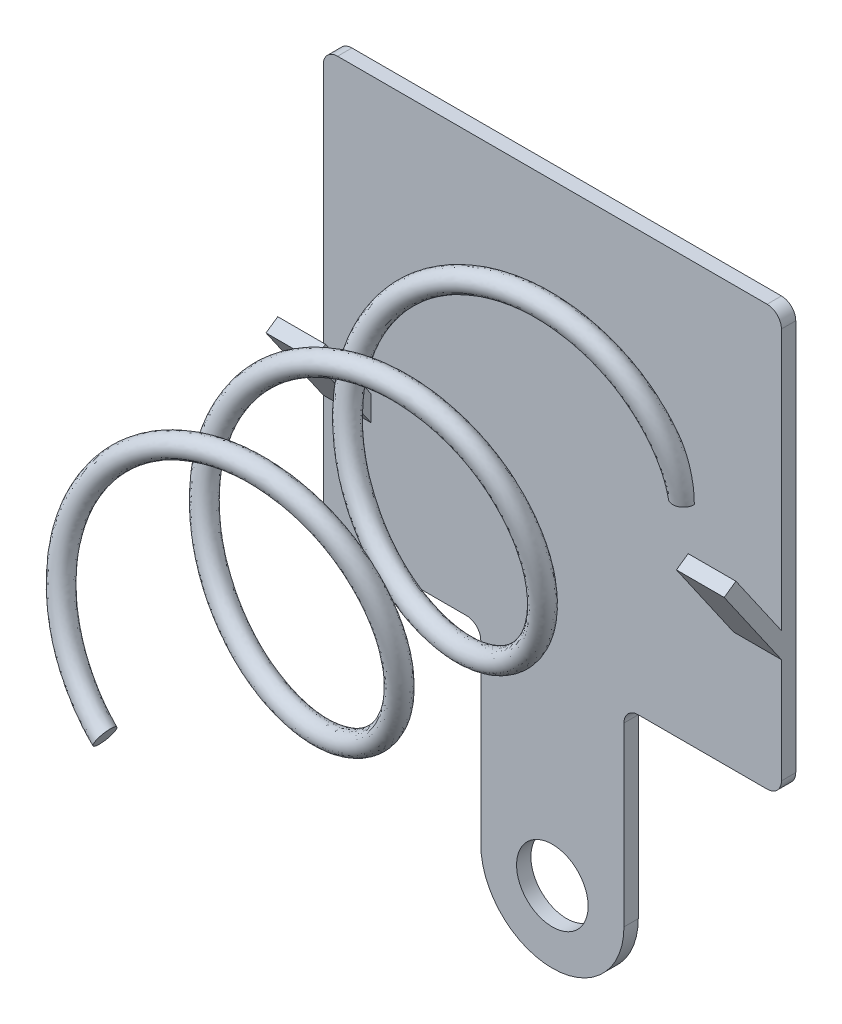
SolidWorks part; units mm, degrees
ref_plane "Front Plane" through (0, 0, 0) normal (0, 0, 1) x (1, 0, 0)
ref_plane "Top Plane" through (0, 0, 0) normal (0, 1, 0) x (1, 0, 0)
ref_plane "Right Plane" through (0, 0, 0) normal (1, 0, 0) x (0, 0, -1)
sketch "Sketch1" plane through (0, 0, 0) normal (0, 0, 1) x (1, 0, 0)
  line L0 (0, 0) -> (0, 4.4) construction
  line L1 (-4.8, 4.4) -> (4.8, 4.4)
  line L2 (4.8, 4.4) -> (4.8, -4.4)
  line L3 (4.8, -4.4) -> (1.5, -4.4)
  line L4 (1.5, -4.4) -> (1.5, -8.4)
  line L5 (0, 0) -> (0, -8.4) construction
  line L6 (-1.5, -4.4) -> (-1.5, -8.4)
  line L7 (-4.8, -4.4) -> (-1.5, -4.4)
  line L8 (-4.8, 4.4) -> (-4.8, -4.4)
  line L9 (-2.6852, -9.9) -> (3.5735, -9.9) construction
  line L10 (0, 0) -> (4.8, 0) construction
  arc A0 (1.5, -8.4) -> (-1.5, -8.4) centre (0, -8.4) cw
  circle A1 centre (0, -8.4) radius 0.75
  dimension "D5" = 1.5
  dimension "D1" = 9.6
  dimension "D2" = 8.8
  dimension "D3" = 14.3
  dimension "D4" = 3
extrude "Boss-Extrude1" add sketch "Sketch1" along normal blind 0.3
fillet "Fillet1" radius 0.3 6 edges at (-1.5, -4.4, 0.15) (1.5, -4.4, 0.15) (4.8, -4.4, 0.15) (-4.8, -4.4, 0.15) (-4.8, 4.4, 0.15) (4.8, 4.4, 0.15)
sketch "Sketch2" plane through (4.8, 0, 0) normal (1, 0, 0) x (0, 0, -1)
  line L0 (-0.3, -1.9) -> (-1.5, -0.1711)
  line L1 (-0.3, -4.1) -> (-0.3, 4.1) construction
  line L2 (-1.5, -0.1711) -> (-1.2535, 0)
  line L3 (-1.2535, 0) -> (-0.3, -1.3739)
  line L4 (-0.3, -1.3739) -> (-0.3, -1.9)
  line L5 (-0.3, 4.4) -> (0, 4.4) construction
  line L6 (0, -4.1) -> (0, 4.1) construction
  line L7 (0, -4.4) -> (-0.3, -4.4) construction
  dimension "D1" = 0.3
  dimension "D2" = 6.3
  dimension "D3" = 1.5
  dimension "D4" = 4.4
extrude "Boss-Extrude2" add sketch "Sketch2" against normal blind 1
mirror "Mirror1" about plane through (0, 0, 0) normal (1, 0, 0) of "Boss-Extrude2"
sketch "Sketch3" plane through (0, 0, 0.3) normal (0, 0, 1) x (1, 0, 0)
  circle A0 centre (0, 0) radius 2.75
  dimension "D1" = 5.5
curve "Helix/Spiral1" pitch 3 height 8 radius 2.75 centre (0, 0, 0.3) axis (0, 0, 1) start towards (1, 0, 0)
sketch "Sketch4" plane through (0, 0, 0) normal (0, 1, 0) x (1, 0, 0)
  line L0 (4.5, -0.3) -> (-4.5, -0.3) construction
  circle A0 centre (2.75, -0.3) radius 0.225
  spline S0 degree 3 poles (2.75, -0.3) (2.75, -0.3631) (2.6022, -0.4907) (1.9718, -0.6809) (1.0317, -0.8714) (-0.0704, -1.0619) (-1.1614, -1.2524) (-2.0701, -1.4429) (-2.6536, -1.6333) (-2.8204, -1.8238) (-2.5443, -2.0143) (-1.8685, -2.2048) (-0.8994, -2.3952) (0.211, -2.5857) (1.2883, -2.7762) (2.1632, -2.9667) (2.6985, -3.1571) (2.8099, -3.3476) (2.48, -3.5381) (1.7607, -3.7286) (0.7648, -3.919) (-0.3511, -4.1095) (-1.412, -4.3) (-2.251, -4.4905) (-2.7366, -4.681) (-2.7924, -4.8714) (-2.4096, -5.0619) (-1.6484, -5.2524) (-0.6284, -5.4429) (0.4904, -5.6333) (1.5321, -5.8238) (2.3332, -6.0143) (2.7679, -6.2048) (2.7679, -6.3952) (2.3332, -6.5857) (1.5321, -6.7762) (0.4904, -6.9667) (-0.6284, -7.1571) (-1.6484, -7.3476) (-2.4096, -7.5381) (-2.7924, -7.7286) (-2.7363, -7.9191) (-2.252, -8.1093) (-1.6897, -8.2369) (-1.375, -8.3) knots 0 0 0 0 0.02381 0.047619 0.071429 0.095238 0.119048 0.142857 0.166667 0.190476 0.214286 0.238095 0.261905 0.285714 0.309524 0.333333 0.357143 0.380952 0.404762 0.428571 0.452381 0.47619 0.5 0.52381 0.547619 0.571429 0.595238 0.619048 0.642857 0.666667 0.690476 0.714286 0.738095 0.761905 0.785714 0.809524 0.833333 0.857143 0.880952 0.904762 0.928571 0.952381 0.97619 1 1 1 1 construction
  dimension "D1" = 0.45
sweep "Sweep1" add profiles "Sketch4" path "Helix/Spiral1"
